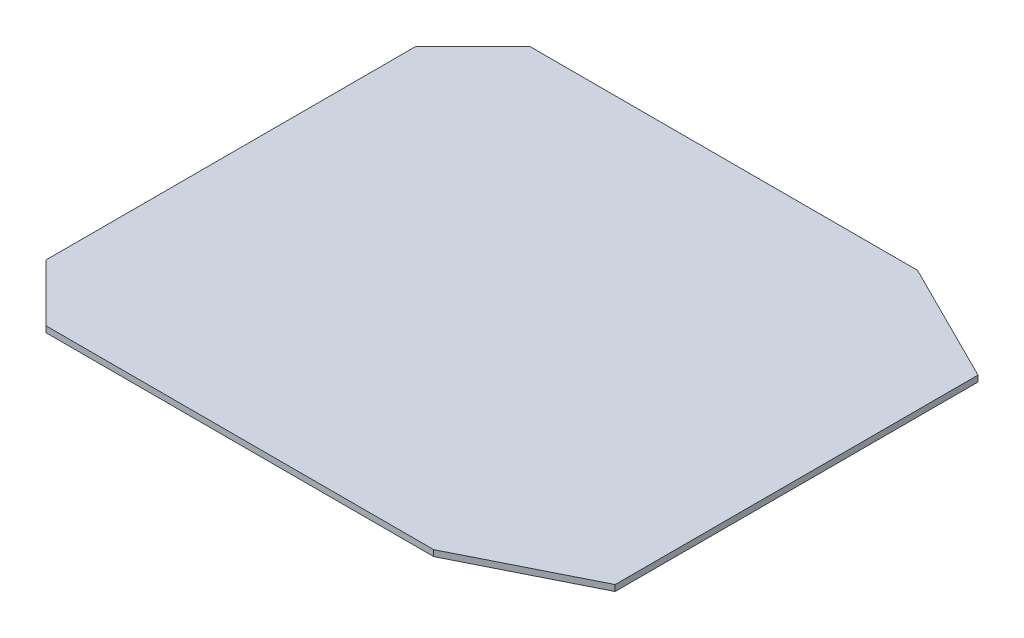
SolidWorks part; units mm, degrees
material "1023 Carbon Steel Sheet (SS)"
ref_plane "Front Plane" through (0, 0, 0) normal (0, 0, 1) x (1, 0, 0)
ref_plane "Top Plane" through (0, 0, 0) normal (0, 1, 0) x (1, 0, 0)
ref_plane "Right Plane" through (0, 0, 0) normal (1, 0, 0) x (0, 0, -1)
sketch "Sketch2" plane through (0, 0, 0) normal (0, 1, 0) x (1, 0, 0)
  line L1 (-392.491, 6.749) -> (-364.2067, -21.5352)
  line L2 (-364.2067, -21.5352) -> (-171.8601, -21.5352)
  line L3 (-171.8601, -21.5352) -> (-111.8601, 8.4648)
  line L4 (-111.8601, 8.4648) -> (-111.8601, 188.4648)
  line L5 (-111.8601, 188.4648) -> (-171.8601, 218.4648)
  line L6 (-171.8601, 218.4648) -> (-364.2067, 218.4648)
  line L7 (-364.2067, 218.4648) -> (-392.491, 190.1805)
  line L9 (-392.491, 6.749) -> (-392.491, 190.1805)
  point P2 (-268.0334, 218.4648)
  point P9 (-392.491, 98.4648)
  point P11 (-111.8601, 98.4648)
  dimension "D1" = 240
  dimension "D2" = 120
  dimension "D3" = 40
  dimension "D4" = 120
  dimension "D5" = 40
  dimension "D6" = 30
  dimension "D7" = 60
extrude "Boss-Extrude1" add sketch "Sketch2" along normal blind 3
